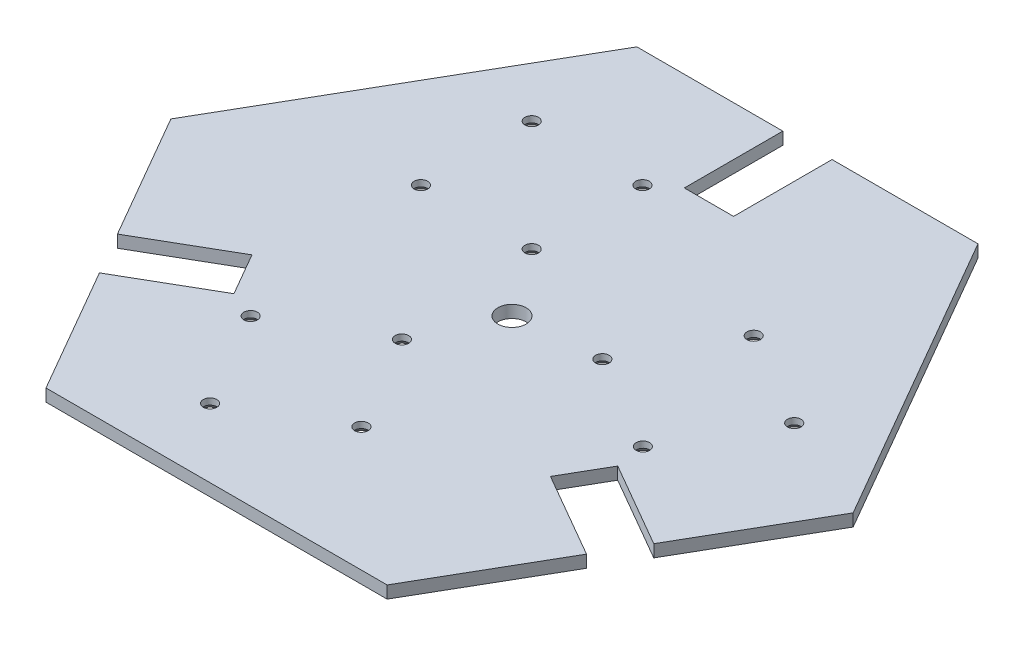
SolidWorks part; units mm, degrees
ref_plane "Front Plane" through (0, 0, 0) normal (0, 0, 1) x (1, 0, 0)
ref_plane "Top Plane" through (0, 0, 0) normal (0, 1, 0) x (1, 0, 0)
ref_plane "Right Plane" through (0, 0, 0) normal (1, 0, 0) x (0, 0, -1)
sketch "Sketch1" plane through (0, 0, 0) normal (0, 1, 0) x (1, 0, 0)
  line L1 (69.282, 120) -> (-69.282, 120)
  line L2 (-69.282, 120) -> (-138.5641, 0)
  line L3 (-138.5641, 0) -> (-69.282, -120)
  line L4 (-69.282, -120) -> (69.282, -120)
  line L5 (69.282, -120) -> (138.5641, 0)
  line L6 (138.5641, 0) -> (69.282, 120)
  circle A0 centre (0, 0) radius 120 construction
  dimension "D1" = 240
extrude "Boss-Extrude1" add sketch "Sketch1" along normal blind 5
sketch "Sketch2" plane through (0, 0, 0) normal (0, 1, 0) x (1, 0, 0)
  line L0 (0, 0) -> (103.923, 60) construction
  line L1 (138.5641, 0) -> (69.282, 120) construction
  line L2 (75.5513, 30.8586) -> (53.0513, -8.1125) construction
  line L3 (66.5368, -29.7548) -> (27.5657, -7.2548) construction
  line L6 (33.5657, 3.1375) -> (72.5368, -19.3625) construction
  line L7 (72.5368, -19.3625) -> (95.0368, 19.6086) construction
  line L8 (95.0368, 19.6086) -> (56.0657, 42.1086) construction
  line L9 (56.0657, 42.1086) -> (33.5657, 3.1375) construction
  line L10 (-14.0657, -30.6375) -> (-53.0368, -53.1375) construction
  line L11 (8.4343, -69.6086) -> (-14.0657, -30.6375) construction
  line L12 (-30.5368, -92.1086) -> (8.4343, -69.6086) construction
  line L13 (-53.0368, -53.1375) -> (-30.5368, -92.1086) construction
  line L14 (-19.5, 27.5) -> (-19.5, 72.5) construction
  line L15 (-64.5, 27.5) -> (-19.5, 27.5) construction
  line L16 (-64.5, 72.5) -> (-64.5, 27.5) construction
  line L17 (-19.5, 72.5) -> (-64.5, 72.5) construction
  line L19 (53.0513, -8.1125) -> (43.3013, -25) construction
  line L21 (103.923, -60) -> (0, 0) construction
  line L22 (69.282, -120) -> (138.5641, 0) construction
  point P9 (47.0513, -18.5048)
  point P18 (33.5657, 3.1375)
  point P19 (56.0657, 42.1086)
  point P20 (95.0368, 19.6086)
  point P21 (72.5368, -19.3625)
  point P31 (0, 0)
  dimension "D1" = 45
  dimension "D2" = 45
  dimension "D4" = 7.5
  dimension "D5" = 12
  dimension "D6" = 50
  dimension "D3" = 3
sketch "Sketch5" plane through (0, 5, 0) normal (0, 1, 0) x (1, 0, 0)
  circle A0 centre (0, 0) radius 5.7532
extrude "Cut-Extrude1" cut sketch "Sketch5" against normal through all
hole_wizard "CSK for M5 Flat Head Machine Screw1" positions "Sketch7" profile "Sketch6" countersink size "M5" standard "ANSI Metric" end condition through all
sketch "Sketch7" plane through (0, 0, 0) normal (0, -1, 0) x (-1, 0, 0)
  point P0 (64.5, 27.5)
  point P3 (19.5, 27.5)
  point P6 (19.5, 72.5)
  point P9 (64.5, 72.5)
  point P12 (-33.5657, 3.1375)
  point P15 (-72.5368, -19.3625)
  point P18 (-95.0368, 19.6086)
  point P21 (-56.0657, 42.1086)
  point P24 (14.0657, -30.6375)
  point P27 (-8.4343, -69.6086)
  point P30 (30.5368, -92.1086)
  point P33 (53.0368, -53.1375)
sketch "Sketch6" plane through (-64.5, 0, -27.5) normal (1, 0, 0) x (0, 0, -1)
  line L0 (0, 0) -> (0, 5)
  line L1 (0, 5) -> (2.75, 5)
  line L2 (2.75, 5) -> (2.75, 2.45)
  line L3 (2.75, 2.45) -> (5.2, 0)
  line L5 (5.2, 0) -> (0, 0)
  line L6 (-2.75, 2.45) -> (-5.2, 0) construction
  line L11 (0, -6.35) -> (0, 107.95) construction
  dimension "Thru Hole Dia." = 5.5
  dimension "Thru Hole Depth" = 5
  dimension "Near C'Sink Dia." = 10.4
  dimension "Near C'Sink Angle" = 90
sketch "Sketch8" plane through (0, 0, 0) normal (0, -1, 0) x (1, 0, 0)
  line L0 (98.923, 68.6603) -> (108.923, 51.3397)
  line L1 (98.923, 68.6603) -> (64.282, 48.6603)
  line L2 (108.923, 51.3397) -> (74.282, 31.3397)
  line L3 (64.282, 48.6603) -> (74.282, 31.3397)
  line L4 (69.282, 120) -> (138.5641, 0) construction
  line L5 (103.923, 60) -> (0, 0) construction
  line L6 (53.0513, 8.1125) -> (43.3013, 25) construction
  line L7 (10, -120) -> (-10, -120)
  line L8 (10, -120) -> (10, -80)
  line L9 (-10, -120) -> (-10, -80)
  line L10 (10, -80) -> (-10, -80)
  line L11 (-108.923, 51.3397) -> (-98.923, 68.6603)
  line L12 (-108.923, 51.3397) -> (-74.282, 31.3397)
  line L13 (-98.923, 68.6603) -> (-64.282, 48.6603)
  line L14 (-74.282, 31.3397) -> (-64.282, 48.6603)
  point P6 (103.923, 60)
  point P22 (0, 0)
  dimension "D1" = 20
  dimension "D2" = 30
  dimension "D3" = 3
extrude "Cut-Extrude2" cut sketch "Sketch8" against normal through all
